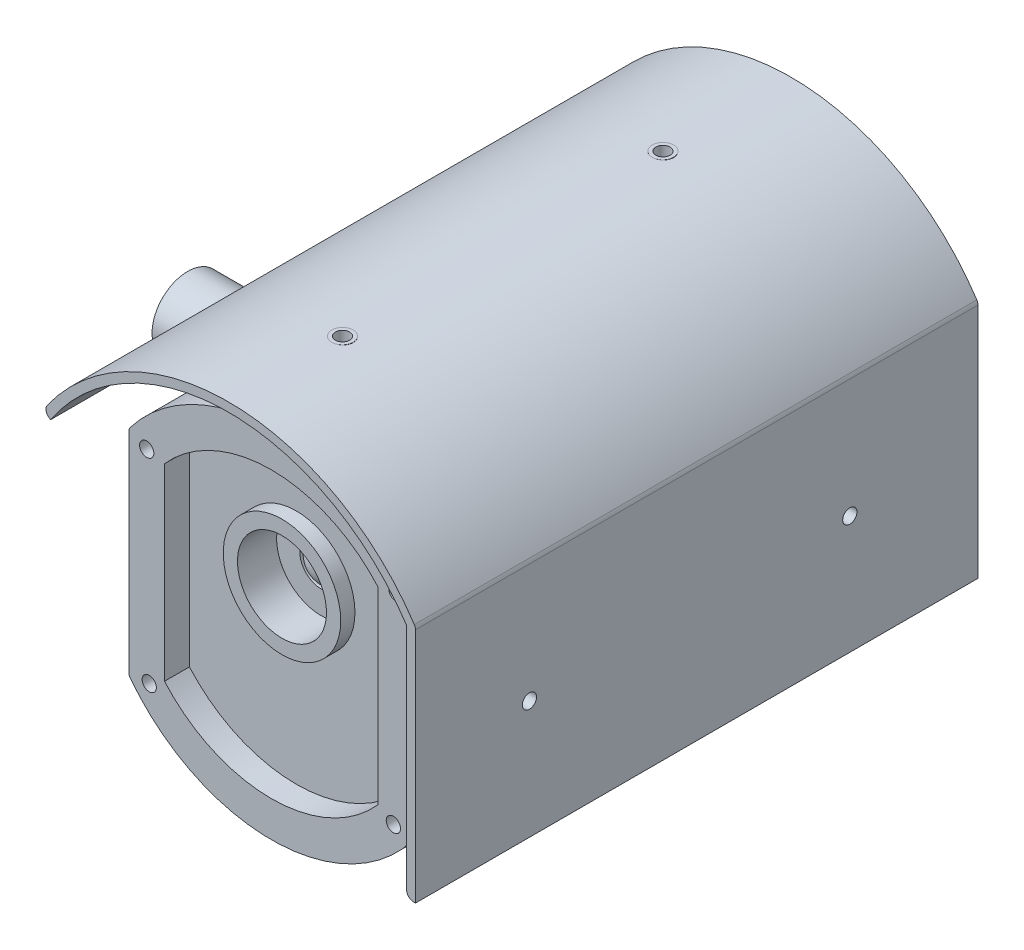
SolidWorks part; units mm, degrees
ref_plane "Front Plane" through (0, 0, 0) normal (0, 0, 1) x (1, 0, 0)
ref_plane "Top Plane" through (0, 0, 0) normal (0, 1, 0) x (1, 0, 0)
ref_plane "Right Plane" through (0, 0, 0) normal (1, 0, 0) x (0, 0, -1)
sketch "Sketch1" plane through (0, 0, 0) normal (0, 0, 1) x (1, 0, 0)
  line L2 (-40, -30) -> (-40, 30)
  line L3 (40, -30) -> (40, 30)
  line L5 (40, 0) -> (-40, 0) construction
  arc A0 (40, 30) -> (-40, 30) centre (0, 0) ccw
  arc A1 (40, -30) -> (-40, -30) centre (0, 0) cw
  point P18 (40, 0)
  point P19 (-40, 0)
  dimension "D1" = 60
  dimension "D2" = 80
extrude "Boss-Extrude1" add sketch "Sketch1" along normal blind 140
sketch "Sketch2" plane through (0, 0, 140) normal (0, 0, 1) x (1, 0, 0)
  line L4 (-30, 26.4575) -> (-30, -26.4575)
  line L5 (30, -26.4575) -> (30, 26.4575)
  line L6 (-30, 26.4575) -> (-30, -26.4575)
  line L7 (30, -26.4575) -> (30, 26.4575)
  arc A4 (30, 26.4575) -> (-30, 26.4575) centre (0, 0) ccw
  arc A5 (-30, -26.4575) -> (30, -26.4575) centre (0, 0) ccw
  arc A6 (30, 26.4575) -> (-30, 26.4575) centre (0, 0) ccw
  arc A7 (-30, -26.4575) -> (30, -26.4575) centre (0, 0) ccw
  dimension "D1" = 10
extrude "Cut-Extrude1" cut sketch "Sketch2" against normal blind 7
sketch "Sketch3" plane through (0, 0, 140) normal (0, 0, 1) x (1, 0, 0)
  line L2 (52.5, -33.1662) -> (52.5, 33.9116)
  line L3 (-50, 33.1662) -> (-52.0833, 34.5482)
  line L4 (-50, 33.1662) -> (-50, -33.1662)
  line L5 (50, -33.1662) -> (50, 33.1662)
  line L6 (52.5, -33.1662) -> (50, -33.1662)
  line L7 (50, -33.1662) -> (50, 33.1662)
  arc A2 (52.5, 33.9116) -> (-52.0833, 34.5482) centre (0, 0) ccw
  arc A4 (50, 33.1662) -> (-50, 33.1662) centre (0, 0) ccw
  arc A5 (-50, -33.1662) -> (50, -33.1662) centre (0, 0) ccw
  arc A6 (50, 33.1662) -> (-50, 33.1662) centre (0, 0) ccw
  dimension "D1" = 10
  dimension "D2" = 2.5
extrude "Boss-Extrude2" add sketch "Sketch3" along normal blind 12 and the other way blind 146 separate body
sketch "Sketch4" plane through (0, 0, 133) normal (0, 0, 1) x (1, 0, 0)
  circle A0 centre (0, 10) radius 12.5
  circle A1 centre (0, 10) radius 16.5
  dimension "D1" = 25
  dimension "D2" = 10
  dimension "D3" = 4
extrude "Boss-Extrude3" add sketch "Sketch4" along normal blind 4
sketch "Sketch5" plane through (0, 0, 133) normal (0, 0, 1) x (1, 0, 0)
  circle A1 centre (0, 10) radius 12.5
  circle A2 centre (0, 10) radius 12.5
  dimension "D1" = 0
extrude "Cut-Extrude2" cut sketch "Sketch5" against normal blind 7
sketch "Sketch6" plane through (0, 0, 126) normal (0, 0, 1) x (1, 0, 0)
  circle A0 centre (0, 10) radius 6
  dimension "D1" = 12
extrude "Cut-Extrude3" cut sketch "Sketch6" against normal blind 1
dome "Dome1" faces to dome 1 distance 3 reverse direction no elliptical dome no face at (6, 10, 125) parameters "D1"=3
sketch "Sketch7" plane through (52.5, 0, 0) normal (1, 0, 0) x (0, 0, -1)
  circle A0 centre (-120, 0) radius 3
  circle A1 centre (-30, 0) radius 3
  dimension "D3" = 6
  dimension "D1" = 90
  dimension "D2" = 30
extrude "Boss-Extrude4" add sketch "Sketch7" against normal up to surface (12.5 mm away) up to face at (40, 0, 70)
sketch "Sketch8" plane through (52.5, 0, 0) normal (1, 0, 0) x (0, 0, -1)
  circle A6 centre (-120, 0) radius 2
  circle A8 centre (-30, 0) radius 2
  dimension "D1" = 4
extrude "Cut-Extrude4" cut sketch "Sketch8" against normal blind 17
ref_plane "Plane1" through (0, 62.5, 0) normal (0, 1, 0) x (-1, 0, 0)
sketch "Sketch9" plane through (0, 62.5, 0) normal (0, 1, 0) x (-1, 0, 0)
  line L0 (-52.5, 120) -> (0, 120) construction
  line L1 (-52.5, 123) -> (-52.5, 117) construction
  circle A0 centre (0, 120) radius 3
  circle A1 centre (0, 30) radius 3
  dimension "D2" = 6
  dimension "D1" = 90
extrude "Boss-Extrude5" add sketch "Sketch9" against normal up to surface (12.5 mm away) up to face at (0, 40, 70)
sketch "Sketch10" plane through (0, 62.5, 0) normal (0, 1, 0) x (1, 0, 0)
  circle A0 centre (0, -30) radius 2
  circle A1 centre (0, -120) radius 2
  arc A2 (0, -123) -> (0, -117) centre (0, -120) ccw construction
  dimension "D1" = 4
extrude "Cut-Extrude5" cut sketch "Sketch10" against normal blind 17
sketch "Sketch11" plane through (0, 0, 0) normal (0, 0, -1) x (-1, 0, 0)
  line L4 (-42, 30.6594) -> (-42, -30.6594)
  line L5 (42, -30.6594) -> (42, 30.6594)
  line L6 (-42, 30.6594) -> (-42, -30.6594)
  line L7 (42, -30.6594) -> (42, 30.6594)
  line L8 (-40, 30) -> (-40, -30)
  line L9 (40, -30) -> (40, 30)
  line L10 (-40, 30) -> (-40, -30)
  line L11 (40, -30) -> (40, 30)
  arc A4 (42, 30.6594) -> (-42, 30.6594) centre (0, 0) ccw
  arc A5 (-42, -30.6594) -> (42, -30.6594) centre (0, 0) ccw
  arc A6 (42, 30.6594) -> (-42, 30.6594) centre (0, 0) ccw
  arc A7 (-42, -30.6594) -> (42, -30.6594) centre (0, 0) ccw
  arc A8 (40, 30) -> (-40, 30) centre (0, 0) ccw
  arc A9 (-40, -30) -> (40, -30) centre (0, 0) ccw
  arc A10 (40, 30) -> (-40, 30) centre (0, 0) ccw
  arc A11 (-40, -30) -> (40, -30) centre (0, 0) ccw
  dimension "D1" = 2
  dimension "D2" = 0
extrude "Boss-Extrude6" add sketch "Sketch11" against normal blind 7
sketch "Sketch12" plane through (0, 0, 0) normal (0, 0, -1) x (-1, 0, 0)
  line L0 (-35, -2.5) -> (35, -2.5)
  line L1 (-35, -6) -> (35, -6)
  line L2 (-35, -12) -> (35, -12)
  line L3 (-35, -8.5) -> (35, -8.5)
  line L4 (-35, 0) -> (35, 0)
  line L5 (-35, 3.5) -> (35, 3.5)
  line L6 (-35, 28.2843) -> (-35, -28.2843)
  line L7 (35, -28.2843) -> (35, 28.2843)
  line L8 (-35, 28.2843) -> (-35, -28.2843)
  line L9 (35, -28.2843) -> (35, 28.2843)
  line L10 (-35, 6) -> (35, 6)
  line L11 (-35, 9.5) -> (35, 9.5)
  line L12 (-35, 12) -> (35, 12)
  line L13 (-35, 15.5) -> (35, 15.5)
  line L14 (-35, 18) -> (35, 18)
  line L15 (-35, 21.5) -> (35, 21.5)
  line L16 (-35, 24) -> (35, 24)
  line L17 (-35, 27.5) -> (35, 27.5)
  line L18 (-33.541, 30) -> (33.541, 30)
  line L19 (-30.0458, 33.5) -> (30.0458, 33.5)
  line L20 (-27, 36) -> (27, 36)
  line L21 (-21.5581, 39.5) -> (21.5581, 39.5)
  line L22 (-16.1555, 42) -> (16.1555, 42)
  line L23 (-35, -18) -> (35, -18)
  line L24 (-35, -14.5) -> (35, -14.5)
  line L25 (-35, -24) -> (35, -24)
  line L26 (-35, -20.5) -> (35, -20.5)
  line L27 (-33.541, -30) -> (33.541, -30)
  line L28 (-35, -26.5) -> (35, -26.5)
  line L29 (-35, 45.5) -> (35, 45.5) [skipped]
  line L30 (-27, -36) -> (27, -36)
  line L31 (-31.1247, -32.5) -> (31.1247, -32.5)
  line L32 (-16.1555, -42) -> (16.1555, -42)
  line L33 (-23.297, -38.5) -> (23.297, -38.5)
  arc A7 (35, 28.2843) -> (-35, 28.2843) centre (0, 0) ccw
  arc A8 (-35, -28.2843) -> (35, -28.2843) centre (0, 0) ccw
  arc A9 (35, 28.2843) -> (-35, 28.2843) centre (0, 0) ccw
  arc A10 (-35, -28.2843) -> (35, -28.2843) centre (0, 0) ccw
  dimension "D2" = 3.5
  dimension "D4" = 2.5
  dimension "D5" = 3.5
  dimension "D1" = 7
  dimension "D3" = 8
  dimension "D6" = 7
extrude "Cut-Extrude6" cut sketch "Sketch12" against normal blind 5 contours L22 A9 | L20 A9 L21 | L18 A9 L19 | L17 L8 L16 L9 | L15 L8 L14 L9 | L13 L8 L12 L9 | L11 L8 L10 L9 | L4 L9 L5 L8 | L1 L9 L0 L8 | L2 L9 L3 L8 | L24 L8 L23 L9 | L26 L8 L25 L9 | L8 A10 L27 L9 L28 | L31 A10 L30 | L33 A10 L32 region at (0, -4.25, 0) region at (0, 1.75, 0) region at (0, -10.25, 0) region at (0, 7.75, 0) region at (0, -16.25, 0) region at (0, 13.75, 0) region at (0, -22.25, 0) region at (0, 19.75, 0) region at (0, -28.238, 0) region at (0, 25.75, 0) region at (0, -34.2088, 0) region at (0, 31.718, 0) region at (0, -40.1467, 0) region at (0, 37.6852, 0) region at (0, 43.2035, 0)
sketch "Sketch13" plane through (-40, 0, 0) normal (-1, 0, 0) x (0, 0, 1)
  line L0 (73.5, -30) -> (73.5, 0) construction
  line L1 (140, -30) -> (7, -30) construction
  circle A0 centre (73.5, 0) radius 10
  dimension "D1" = 20
extrude "Boss-Extrude7" add sketch "Sketch13" along normal blind 50
sketch "Sketch14" plane through (-40, 0, 0) normal (-1, 0, 0) x (0, 0, 1)
  circle A0 centre (73.5, 0) radius 10 construction
  circle A1 centre (73.5, 0) radius 10
  circle A2 centre (73.5, 0) radius 15
  dimension "D1" = 5
extrude "Boss-Extrude8" add sketch "Sketch14" along normal blind 20
fillet "Fillet1" radius 2 24 edges at (40, -3, 30) (40, -3, 120) (50, -3, 30) (50, -3, 120) (-0.684, 49.9953, 27.079) (0.6858, 59.9961, 27.0794) (-0.684, 49.9953, 117.079) (0.6858, 59.9961, 117.0794) (-40, 30, 73.5) (-40, -30, 73.5) (40, -30, 73.5) (40, 30, 73.5) (52.5, 33.9116, 73) (50, -33.1662, 73) (-52.0833, 34.5482, 73) (-40, 15, 73.5) (42, 30.6594, 3.5) (42, -30.6594, 3.5) (0, -52, 0) (42, 0, 0) (0, 52, 0) (-42, 30.6594, 3.5) (-42, -30.6594, 3.5) (-42, 0, 0)
sketch "Sketch15" plane through (0, 0, 140) normal (0, 0, 1) x (1, 0, 0)
  circle A0 centre (35, 27.5) radius 2
  circle A1 centre (-35, 27.5) radius 2
  circle A3 centre (34.2812, -29.1513) radius 2
  arc A4 (33.541, -30) -> (35, -28.2843) centre (0, 0) ccw construction
  circle A5 centre (-34.2812, -29.1513) radius 2
  arc A6 (-35, -28.2843) -> (-33.541, -30) centre (0, 0) ccw construction
  dimension "D1" = 4
extrude "Cut-Extrude7" cut sketch "Sketch15" against normal blind 5
scale "Ölçek1" bodies to scale 115 scale about centroid uniform scaling yes scale factor 0.1
